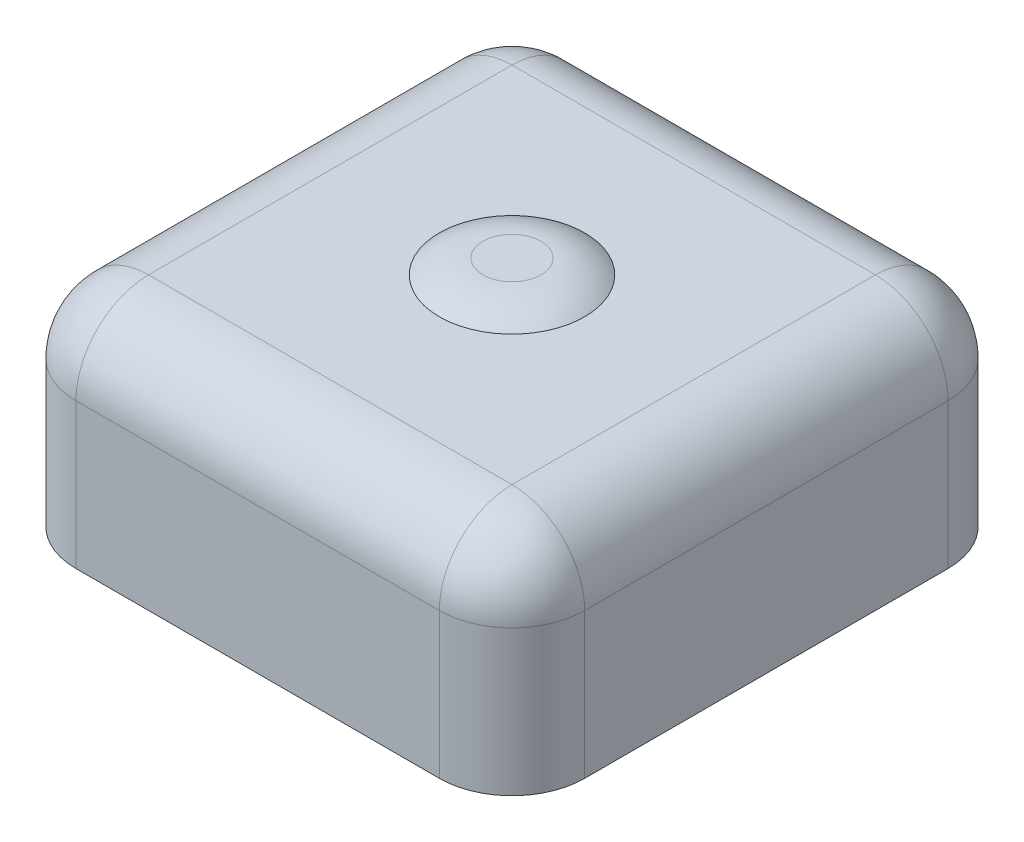
SolidWorks part; units mm, degrees
ref_plane "Front Plane" through (0, 0, 0) normal (0, 0, 1) x (1, 0, 0)
ref_plane "Top Plane" through (0, 0, 0) normal (0, 1, 0) x (1, 0, 0)
ref_plane "Right Plane" through (0, 0, 0) normal (1, 0, 0) x (0, 0, -1)
sketch "Sketch1" plane through (0, 0, 0) normal (0, 1, 0) x (1, 0, 0)
  line L1 (-3.5, 3.5) -> (3.5, 3.5)
  line L2 (-3.5, 3.5) -> (-3.5, -3.5)
  line L3 (-3.5, -3.5) -> (3.5, -3.5)
  line L4 (3.5, 3.5) -> (3.5, -3.5)
  line L5 (-3.5, 3.5) -> (3.5, -3.5) construction
  line L6 (-3.5, -3.5) -> (3.5, 3.5) construction
  point P0 (0, 0)
  dimension "D1" = 7
  dimension "D2" = 7
extrude "Boss-Extrude1" add sketch "Sketch1" along normal blind 3
fillet "Fillet1" radius 1 8 edges at (3.5, 1.5, -3.5) (-3.5, 1.5, -3.5) (-3.5, 1.5, 3.5) (3.5, 1.5, 3.5) (0, 3, -3.5) (-3.5, 3, 0) (0, 3, 3.5) (3.5, 3, 0)
sketch "Sketch2" plane through (0, 3, 0) normal (0, 1, 0) x (1, 0, 0)
  circle A0 centre (0, 0) radius 1
extrude "Boss-Extrude2" add sketch "Sketch2" along normal blind 0.2
fillet "Fillet2" radius 1 1 edges at (0, 3.2, 1)
